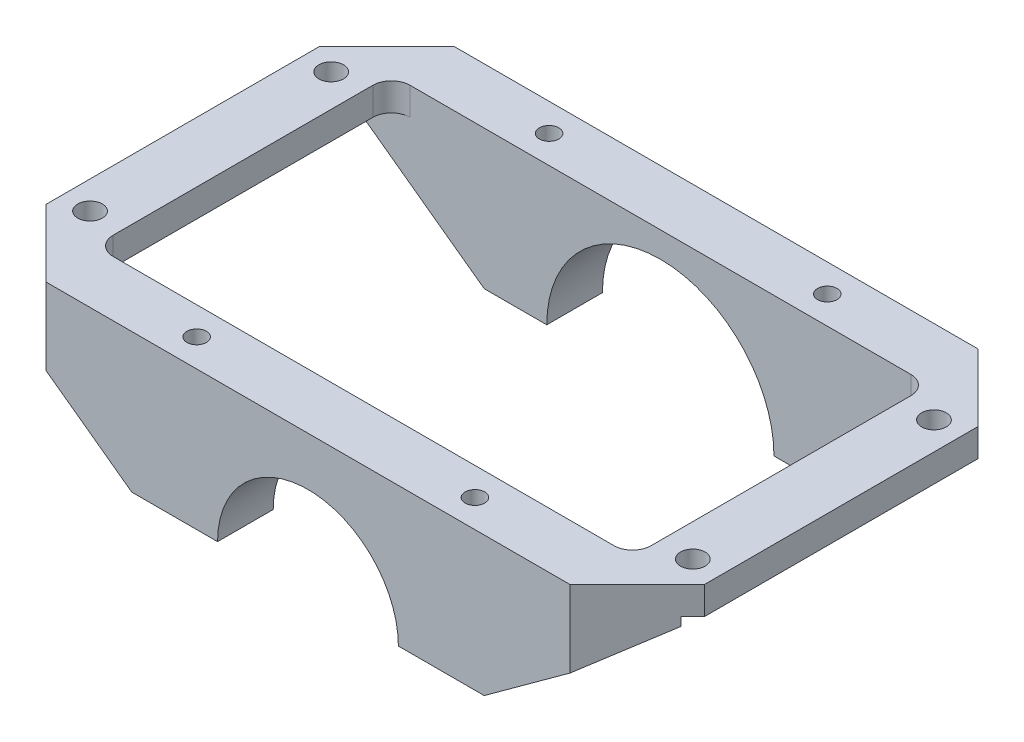
SolidWorks part; units mm, degrees
ref_plane "前视基准面" through (0, 0, 0) normal (0, 0, 1) x (1, 0, 0)
ref_plane "上视基准面" through (0, 0, 0) normal (0, 1, 0) x (1, 0, 0)
ref_plane "右视基准面" through (0, 0, 0) normal (1, 0, 0) x (0, 0, -1)
sketch "草图1" plane through (0, 0, 0) normal (0, 1, 0) x (1, 0, 0)
  line L0 (-6.4392, 0) -> (31.064, 0) construction
  line L1 (0, 0) -> (0, 31.3242) construction
  line L3 (-71, 44) -> (71, 44)
  line L4 (-71, 44) -> (-71, -44)
  line L5 (-71, -44) -> (71, -44)
  line L6 (71, 44) -> (71, -44)
  line L7 (-58, 32) -> (58, 32)
  line L8 (-58, 32) -> (-58, -32)
  line L9 (-58, -32) -> (58, -32)
  line L10 (58, 32) -> (58, -32)
  dimension "D1" = 142
  dimension "D2" = 88
  dimension "D3" = 64
  dimension "D4" = 116
extrude "凸台-拉伸1" add sketch "草图1" against normal blind 30
sketch "草图2" plane through (0, 0, 44) normal (0, 0, 1) x (1, 0, 0)
  line L0 (0, -30) -> (0, 9.4031) construction
  line L1 (-71, -6) -> (-38, -30)
  line L2 (-38, -30) -> (-71, -30)
  line L3 (-71, -30) -> (-71, -6)
  line L4 (71, 0) -> (-71, 0)
  line L5 (-71, 0) -> (-71, -30)
  line L6 (-71, -30) -> (71, -30)
  line L9 (-71, 0) -> (-71, -30)
  line L10 (71, 0) -> (-71, 0) construction
  line L11 (71, -30) -> (71, 0)
  line L12 (-71, -30) -> (71, -30) construction
  line L13 (71, -30) -> (71, 0)
  line L14 (71, -30) -> (71, -6)
  line L15 (38, -30) -> (71, -30)
  line L16 (71, -6) -> (38, -30)
  line M38 (-71, -30) -> (71, -30)
  line M39 (71, -30) -> (71, 0)
  dimension "D1" = 0
  dimension "D2" = 6
  dimension "D3" = 76
extrude "切除-拉伸1" cut sketch "草图2" against normal through all contours L16 M39 M38 | L3 L1 L2 region at (60, -22, 44)
sketch "草图4" plane through (-71, 0, 0) normal (-1, 0, 0) x (0, 0, 1)
  line L0 (0, 0) -> (0, 10.8712) construction
  line L1 (-32, -15.4545) -> (-32, -30) construction
  line L3 (-32, -15.4545) -> (-32, -30) construction
  line L4 (-44, -6) -> (44, -6)
  line L5 (-44, -6) -> (44, -6)
  line L6 (44, 0) -> (-44, 0)
  line L7 (44, -6) -> (44, 0)
  line L8 (44, -6) -> (44, 0)
  line L9 (-44, 0) -> (-44, -6)
  line L10 (44, 0) -> (-44, 0) construction
  line L11 (-44, 0) -> (-44, -6)
  line L13 (-32, -22.7273) -> (32, -22.7273)
  line L14 (-32, -22.7273) -> (-32, -6)
  line L15 (-32, -6) -> (32, -6)
  line L16 (32, -22.7273) -> (32, -6)
  dimension "D1" = 0
extrude "切除-拉伸2" cut sketch "草图4" against normal through all contours L13 L16 L5 L14 region at (-71, -14.3636, 0)
fillet "圆角3" radius 4 4 edges at (58, -3, 32) (58, -3, -32) (-58, -3, 32) (-58, -3, -32)
chamfer "倒角2" distance 14.5 4 edges at (71, -3, 44) (71, -3, -44) (-71, -3, 44) (-71, -3, -44)
sketch "草图8" plane through (0, 0, 44) normal (0, 0, 1) x (1, 0, 0)
  line L1 (-38, -30) -> (38, -30) construction
  circle A0 centre (0, -30) radius 19.5
  point P0 (0, -30)
extrude "切除-拉伸4" cut sketch "草图8" against normal up to next
sketch "草图9" plane through (0, 0, -44) normal (0, 0, -1) x (-1, 0, 0)
  line L0 (-38, -30) -> (38, -30) construction
  circle A0 centre (0, -30) radius 24.5
extrude "切除-拉伸5" cut sketch "草图9" against normal up to next
hole_wizard "4 x M5 螺纹孔" positions "草图19" profile "草图20" tap size "M5" standard "GB" end condition up to next
sketch "草图19" plane through (0, 0, 0) normal (0, 1, 0) x (-1, 0, 0)
  line L0 (0, 0) -> (-16.4766, 0) construction
  line L1 (0, 0) -> (0, -16.1223) construction
  line L3 (-54, -32) -> (54, -32) construction
  point P0 (30, -38)
  point P13 (-30, -38)
  point P15 (-30, 38)
  point P16 (30, 38)
  dimension "D1" = 60
  dimension "D2" = 6
sketch "草图20" plane through (-30, 0, -38) normal (1, 0, 0) x (0, 0, 1)
  line L0 (0, 0) -> (0, 30)
  line L1 (0, 30) -> (2.1, 30)
  line L2 (2.1, 30) -> (2.1, 0)
  line L5 (2.1, 0) -> (0, 0)
  line L11 (0, -6.35) -> (0, 40.2039) construction
  dimension "通孔螺纹孔钻头直径" = 4.2
  dimension "通孔螺纹孔钻头深度" = 30
cosmetic thread "孔螺蚊线6" parameters "D2"=5
cosmetic thread "孔螺蚊线7" parameters "D2"=5
cosmetic thread "孔螺蚊线8" parameters "D2"=5
cosmetic thread "孔螺蚊线9" parameters "D2"=5
hole_wizard "4 x M5 通孔" positions "草图22" profile "草图21" hole size "M5" standard "GB" end condition up to next
sketch "草图22" plane through (0, 0, 0) normal (0, 1, 0) x (-1, 0, 0)
  line L0 (0, 0) -> (-14.9661, 0) construction
  line L1 (0, 0) -> (0, 20.7286) construction
  point P0 (65, -26)
  point P11 (-65, -26)
  point P13 (65, 26)
  point P14 (-65, 26)
  dimension "D1" = 130
  dimension "D2" = 52
sketch "草图21" plane through (-65, 0, -26) normal (1, 0, 0) x (0, 0, 1)
  line L0 (0, 0) -> (0, 6)
  line L1 (0, 6) -> (2.65, 6)
  line L2 (2.65, 6) -> (2.65, 0)
  line L5 (2.65, 0) -> (0, 0)
  line L11 (0, -6.35) -> (0, 22.931) construction
  dimension "通孔孔直径" = 5.3
  dimension "通孔孔深度" = 6
